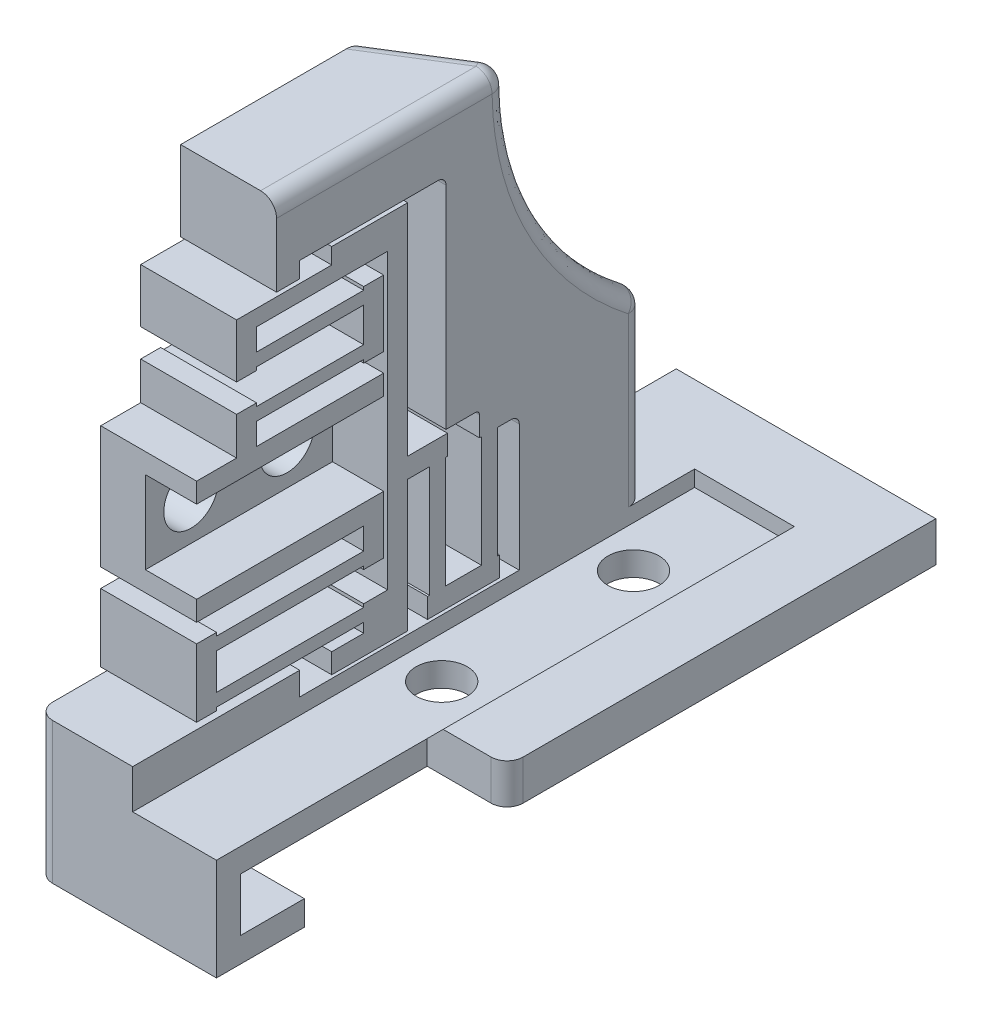
SolidWorks part; units mm, degrees
other "Markup1"
sketch "Sketch8" plane through (10.5, 0, 3) normal (0.7095, 0.0467, 0.7031) x (0.7044, -0.0184, -0.7096)
ref_plane "Front Plane" through (0, 0, 0) normal (0, 0, 1) x (1, 0, 0)
ref_plane "Top Plane" through (0, 0, 0) normal (0, 1, 0) x (1, 0, 0)
ref_plane "Right Plane" through (0, 0, 0) normal (1, 0, 0) x (0, 0, -1)
sketch "Sketch1" plane through (0, 0, 0) normal (1, 0, 0) x (0, 0, -1)
  line L0 (-1.25, -12.7333) -> (6.7, -12.7333)
  line L1 (6.7, -12.7333) -> (6.7, -22.75)
  line L2 (-5, -12.7333) -> (-5, -20.3833)
  line L3 (-5, -20.3833) -> (5.45, -20.3833)
  line L57 (-3.75, -22.55) -> (-3.75, -24.8)
  line L58 (-3.75, -24.8) -> (5.45, -24.8)
  line L60 (5.45, -20.3833) -> (5.45, -21.75)
  line L62 (-5, -21.55) -> (-5, -25.8)
  line L64 (6.95, -6.25) -> (6.95, -24.6)
  line L65 (-1.25, -11.3667) -> (5.45, -11.3667)
  line L66 (5.45, -10.5667) -> (5.45, -8.4167)
  line L68 (-2.5, -8.6167) -> (-2.5, -5.25)
  line L69 (-1.25, -12.7333) -> (-1.25, -11.3667)
  line L71 (6.7, -11.5667) -> (6.7, -7.4167)
  line L73 (-1.25, -7.6167) -> (-1.25, -6.25)
  line L74 (-1.25, -6.25) -> (6.95, -6.25)
  line L75 (-2.5, -5.25) -> (3.45, -5.25)
  line L79 (5.45, -11.3667) -> (5.45, -11.5667)
  line L80 (5.45, -11.5667) -> (6.7, -11.5667)
  line L85 (5.45, -10.5667) -> (-1.25, -10.5667)
  line L86 (-1.25, -10.5667) -> (-1.25, -10.3667)
  line L87 (-1.25, -10.3667) -> (-2.5, -10.3667)
  line L90 (5.45, -8.4167) -> (-1.25, -8.4167)
  line L91 (-1.25, -8.4167) -> (-1.25, -8.6167)
  line L92 (-1.25, -8.6167) -> (-2.5, -8.6167)
  line L93 (-1.25, -7.6167) -> (5.45, -7.6167)
  line L98 (5.45, -7.6167) -> (5.45, -7.4167)
  line L99 (5.45, -7.4167) -> (6.7, -7.4167)
  line L102 (5.45, -21.75) -> (-3.75, -21.75)
  line L103 (-3.75, -21.75) -> (-3.75, -21.55)
  line L104 (-3.75, -21.55) -> (-5, -21.55)
  line L105 (6.7, -22.75) -> (5.45, -22.75)
  line L106 (5.45, -22.75) -> (5.45, -22.55)
  line L111 (5.45, -22.55) -> (-3.75, -22.55)
  line L115 (5.45, -24.8) -> (5.45, -24.6)
  line L116 (5.45, -24.6) -> (6.95, -24.6)
  line L117 (-5, -25.8) -> (-3.75, -25.8)
  line L118 (-3.75, -25.8) -> (-3.75, -25.6)
  line L119 (-3.75, -25.6) -> (5.45, -25.6)
  line L124 (5.45, -25.6) -> (5.45, -26.2)
  line L126 (5.45, -26.2) -> (3.45, -26.2)
  line L127 (3.45, -26.2) -> (3.45, -27.45)
  line L128 (3.45, -27.45) -> (8.2, -27.45)
  line L130 (12.8167, -26.2) -> (10.5667, -26.2)
  line L131 (10.5667, -26.2) -> (10.5667, -19.2333)
  line L136 (10.5667, -19.2333) -> (10.6917, -19.2333)
  line L141 (12.8167, -19.2333) -> (12.8167, -26.2)
  line L145 (9.5667, -26.2) -> (9.4417, -26.2)
  line L146 (9.5667, -26.2) -> (9.5667, -19.2333)
  line L150 (9.5667, -19.2333) -> (8.2, -19.2333)
  line L153 (8.2, -17.9833) -> (10.6917, -17.9833)
  line L155 (14.6833, -19.2333) -> (13.8167, -19.2333)
  line L160 (13.8167, -19.2333) -> (13.8167, -26.2)
  line L168 (15.1833, -27.7) -> (15.1833, -19.7333)
  line L179 (15.1833, -27.7) -> (1.45, -27.7)
  line L180 (1.45, -27.7) -> (1.45, -26.2)
  line L181 (1.45, -26.2) -> (-9, -26.2)
  line L184 (-9, -30.15) -> (23, -30.15)
  line L187 (23, 0) -> (0, 0)
  line L189 (8.2, -27.45) -> (8.2, -19.2333)
  line L190 (1.45, -5) -> (0, -5)
  line L191 (0, -5) -> (0, 0)
  line L192 (13.9417, -26.2) -> (13.8167, -26.2)
  line L193 (12.4417, -17.7333) -> (10.6, -17.7333)
  line L194 (10.6, -17.7333) -> (10.6, -4.5)
  line L198 (9.4417, -26.2) -> (9.4417, -27.45)
  line L199 (13.9417, -26.2) -> (13.9417, -27.45)
  line L200 (13.9417, -27.45) -> (9.4417, -27.45)
  line L201 (8.2, -17.9833) -> (8.2, -4.25)
  line L203 (12.6917, -19.2333) -> (12.6917, -17.9833)
  line L204 (10.6917, -19.2333) -> (10.6917, -17.9833)
  line L205 (12.6917, -19.2333) -> (12.8167, -19.2333)
  line L212 (-9, -30.15) -> (-9, -26.2)
  line L214 (-2.5, -12.7333) -> (-5, -12.7333)
  line L215 (-2.5, -12.7333) -> (-2.5, -10.3667)
  line L216 (23, 0) -> (23, -30.15)
  line L217 (1.45, -5) -> (1.45, -4)
  line L218 (1.45, -4) -> (10.1, -4)
  line L219 (3.45, -5.25) -> (3.45, -4.25)
  line L220 (3.45, -4.25) -> (8.2, -4.25)
  line L221 (13.8167, -19.2333) -> (15.1833, -19.2333) construction
  arc A4 (14.6833, -19.2333) -> (15.1833, -19.7333) centre (14.6833, -19.7333) cw
  arc A5 (12.6917, -17.9833) -> (12.4417, -17.7333) centre (12.4417, -17.9833) ccw
  arc A6 (10.1, -4) -> (10.6, -4.5) centre (10.1, -4.5) cw
  circle A7 centre (3.85, -16.5583) radius 1.7
  circle A8 centre (-2.15, -16.5583) radius 1.7
  circle A9 centre (-2.15, -16.5583) radius 2.85 construction
  circle A10 centre (3.85, -16.5583) radius 2.85 construction
  point P120 (10.6, -5)
  point P140 (15.1833, -19.2333)
  point P144 (12.6917, -17.7333)
  point P151 (-5, -16.5583)
  point P159 (-1.875, -8.6167)
  dimension "D61" = 0.5
  dimension "D62" = 0.25
  dimension "D66" = 0.5
  dimension "D67" = 3.4
  dimension "D68" = 5.7
  dimension "D3" = 4.25
  dimension "D4" = 0.2
  dimension "D6" = 0.8
  dimension "D9" = 0.8
  dimension "D10" = 1.1667
  dimension "D17" = 0.8
  dimension "D18" = 1.75
  dimension "D21" = 0.8
  dimension "D23" = 1
  dimension "D24" = 0.25
  dimension "D37" = 1.25
  dimension "D40" = 0.25
  dimension "D44" = 1
  dimension "D12" = 7.65
  dimension "D20" = 1.25
  dimension "D26" = 1.25
  dimension "D28" = 0.25
  dimension "D33" = 1.25
  dimension "D49" = 2.4
  dimension "D50" = 0.25
  dimension "D31" = 5
  dimension "D54" = 5
  dimension "D55" = 1.25
  dimension "D65" = 2.5
  dimension "D64" = 2.5
  dimension "D29" = 2
  dimension "D52" = 0.25
  dimension "D56" = 1
  dimension "D69" = 6
  dimension "D39" = 4
  dimension "D51" = 32
  dimension "D22" = 1.1667
  dimension "D53" = 2
  dimension "D19" = 0.2
  dimension "D7" = 0.4
  dimension "D8" = 1.45
  dimension "D11" = 1
  dimension "D13" = 4.5
  dimension "D14" = 2
  dimension "D15" = 30.15
  dimension "D16" = 1.25
  dimension "D25" = 1.25
extrude "Boss-Extrude1" add sketch "Sketch1" along normal blind 6
sketch "Sketch2" plane through (0, 0, 5) normal (0, 0, 1) x (1, 0, 0)
  line L0 (6, -12.7333) -> (6, -20.3833) construction
  line L1 (6, -19.1333) -> (2.8, -19.1333)
  line L2 (6, -19.1333) -> (6, -13.9833)
  line L3 (6, -13.9833) -> (2.8, -13.9833)
  line L4 (2.8, -19.1333) -> (2.8, -13.9833)
  line L5 (6, -12.7333) -> (6, -20.3833) construction
  dimension "D1" = 3.2
  dimension "D2" = 1.25
  dimension "D3" = 1.25
extrude "Cut-Extrude4" cut sketch "Sketch2" against normal up to next
sketch "Sketch3" plane through (0, -30.15, 0) normal (0, -1, 0) x (1, 0, 0)
  line L0 (11.24, -4.18) -> (16.24, -4.18)
  line L1 (0, -31) -> (16.24, -31)
  line L2 (0, -31) -> (0, 9)
  line L4 (11.24, -4.18) -> (11.24, 9)
  line L5 (6, 9) -> (6, -23) construction
  line L7 (16.24, -31) -> (16.24, -4.18)
  line L8 (0, 9) -> (0, -23) construction
  line L9 (11.24, 9) -> (0, 9)
  circle A0 centre (8.6, -7.73) radius 1.6
  circle A1 centre (8.6, -19.73) radius 1.6
  dimension "D3" = 3.2
  dimension "D1" = 13.18
  dimension "D2" = 2.6
  dimension "D4" = 12
  dimension "D5" = 5
  dimension "D6" = 40
  dimension "D7" = 16.73
  dimension "D8" = 11.24
sketch "Sketch7" plane through (0, 0, 0) normal (-1, 0, 0) x (0, 0, 1)
  line L0 (2.5, -12.7333) -> (5, -12.7333) construction
  line L2 (-6.7, -12.7333) -> (-6.7, -22.75) construction
  circle A0 centre (2.15, -16.6083) radius 1.7
  circle A1 centre (-3.85, -16.6083) radius 1.7
  circle A2 centre (2.15, -16.6083) radius 2.85 construction
  circle A3 centre (-3.85, -16.6083) radius 2.85 construction
  dimension "D1" = 3.4
  dimension "D2" = 3.875
  dimension "D5" = 5.7
  dimension "D3" = 6
extrude "Cut-Extrude3" cut sketch "Sketch7" against normal up to next
extrude "Boss-Extrude2" add sketch "Sketch3" against normal blind 2.5
sketch "Sketch12" plane through (0, 0, 9) normal (0, 0, 1) x (1, 0, 0)
  line L0 (6, -26.2) -> (6, -27.65) construction
  line L1 (11.24, -27.65) -> (6, -27.65)
  line L2 (11.24, -27.65) -> (11.24, -28.65)
  line L3 (11.24, -28.65) -> (6, -28.65)
  line L4 (6, -27.65) -> (6, -28.65)
  line L5 (11.24, -27.65) -> (6, -27.65) construction
  dimension "D1" = 1
  dimension "D2" = 5.24
extrude "Cut-Extrude6" cut sketch "Sketch12" against normal blind 35.15
sketch "Sketch14" plane through (0, 0, 0) normal (-1, 0, 0) x (0, 0, 1)
  line L1 (9, -28.7) -> (3.5, -28.7)
  line L2 (9, -28.7) -> (9, -35.03)
  line L3 (9, -35.03) -> (3.5, -35.03)
  line L4 (3.5, -28.7) -> (3.5, -35.03)
  line L5 (-1.45, -26.2) -> (9, -26.2) construction
  line L6 (9, -26.2) -> (9, -30.15) construction
  dimension "D1" = 2.5
  dimension "D2" = 6.33
  dimension "D3" = 5.5
extrude "Boss-Extrude4" add sketch "Sketch14" against normal blind 11.24
sketch "Sketch15" plane through (11.24, 0, 0) normal (1, 0, 0) x (0, 0, -1)
  line L1 (-3.5, -30.15) -> (-7.5, -30.15)
  line L2 (-3.5, -30.15) -> (-3.5, -33.48)
  line L3 (-3.5, -33.48) -> (-7.5, -33.48)
  line L4 (-7.5, -30.15) -> (-7.5, -33.48)
  dimension "D1" = 4
  dimension "D2" = 3.33
extrude "Cut-Extrude7" cut sketch "Sketch15" against normal blind 10.25
ref_plane "Plane2" through (0, 0, 7.1) normal (0, 0, 1) x (1, 0, 0)
ref_axis "Axis1" through (11.24, 27.1504, 7.1) along (0, -1, 0)
mirror "Mirror1" [suppressed] of bodies 111
delete or keep bodies "Body-Delete/Keep 1" [suppressed] type delete bodies bodies 111
ref_plane "Plane1" through (4.8929, 0, -3.0574) normal (-0.848, 0, 0.5299) x (0, -1, 0)
sketch "Sketch10" plane through (4.8929, 0, -3.0574) normal (-0.848, 0, 0.5299) x (0, -1, 0)
  line L0 (30.15, 13.5887) -> (30.15, 7.6324) construction
  line L1 (30.15, 2.9682) -> (30.15, -26.2895) construction
  line L2 (30.15, 12.3167) -> (30.15, -33.4435) construction
  circle A0 centre (0.65, -31.2799) radius 21.5
  dimension "D2" = 43
  dimension "D1" = 43.5966
  dimension "D3" = 29.5
extrude "Cut-Extrude5" cut sketch "Sketch10" against normal blind 25
fillet "Fillet1" radius 1 9 edges at (3.1138, -17.4436, -23) (3, 0, -13.4184) (6, -21.8736, -23) (6, -8.7382, -17.1438) (6, 0, -7.6465) (16.24, -28.9, -4.18) (0.99, -31.815, 7.5) (0, -30.615, 9) (0.495, -30.15, 3.5)
chamfer "Chamfer1" distance 1 angle 45 1 edges at (11.24, -27.65, -15.165)
mirror "Mirror2" [suppressed] of bodies 113
delete or keep bodies "Body-Delete/Keep 2" [suppressed] type delete bodies bodies 113
equation "\"VerticalFlexureWidth\"= 0.8"
equation "\"VerticalFlexureGap\"= 1"
equation "\"VerticalDoubleFlexureWidth\"= 2 * \"VerticalFlexureWidth\" + \"VerticalFlexureGap\""
equation "\"HorizontalFlexureLength\"= 7"
equation "\"FlexureJointWidth\"= 1.25"
equation "\"HeadHeight\"= 7.5"
equation "\"VerticalFlexureLength\"= 18"
equation "\"MinGap\"=0.25"
equation "\"BaseplateHeight+Tolerance\"= 3.33"
equation "\"HeadWidth\"= 13"
equation "\"HorizontalFlexureWidth\"= 1"
equation "\"HorizontalFlexureGap\"= 1"
equation "\"HorizontalDoubleFlexureWidth\"= 2 * \"HorizontalFlexureWidth\" + \"HorizontalFlexureGap\""
equation "\"FlexureWidth\"=0.85"
equation "\"FlexureWideWidth\"= 1.25"
equation "\"FlexureGap\"=1.75"
equation "\"TwinFlexureWidth\"= \"FlexureGap\" + 2 * \"FlexureWideWidth\""
equation "\"D3@Sketch1\"=\"TwinFlexureWidth\""
equation "\"FlexureNeckWidth\"= ( \"FlexureWideWidth\" - \"FlexureWidth\" ) / 2"
equation "\"D4@Sketch1\"=\"FlexureNeckWidth\""
equation "\"D6@Sketch1\"=\"VerticalFlexureWidth\""
equation "\"D9@Sketch1\"=\"VerticalFlexureWidth\""
equation "\"D10@Sketch1\"=\"FlexureGapEdge\""
equation "\"D21@Sketch1\"=\"VerticalFlexureWidth\""
equation "\"D18@Sketch1\"=\"FlexureGap\""
equation "\"FlexureLength\"= 2"
equation "\"MainSupport\"=1.5"
equation "\"D24@Sketch1\"=\"MinGap\""
equation "\"D37@Sketch1\"=\"FlexureJointWidth\""
equation "\"D40@Sketch1\"=\"MinGap\""
equation "\"D44@Sketch1\"=\"HorizontalFlexureWidth\""
equation "\"D20@Sketch1\"=\"MainSupport\"-0.25"
equation "\"D26@Sketch1\"=\"FlexureJointWidth\""
equation "\"D28@Sketch1\"=\"MinGap\""
equation "\"D33@Sketch1\"=\"FlexureJointWidth\""
equation "\"FlexureGapEdge\"= \"FlexureGap\" * ( 2 / 3 )"
equation "\"D55@Sketch1\"=\"FlexureJointWidth\""
equation "\"FlexurePlateConnectionHeigh\"= 5.15 + 2.5"
equation "\"D12@Sketch1\"=\"FlexurePlateConnectionHeigh\""
equation "\"D52@Sketch1\"=\"MinGap\""
equation "\"D17@Sketch1\"=\"VerticalFlexureWidth\""
equation "\"D22@Sketch1\"=\"FlexureGapEdge\""
equation "\"D19@Sketch1\"=\"FlexureNeckWidth\""
equation "\"D11@Sketch1\"=\"HorizontalFlexureWidth\""
equation "\"D16@Sketch1\"=\"FlexureJointWidth\""
equation "\"D25@Sketch1\"=\"FlexureJointWidth\""
